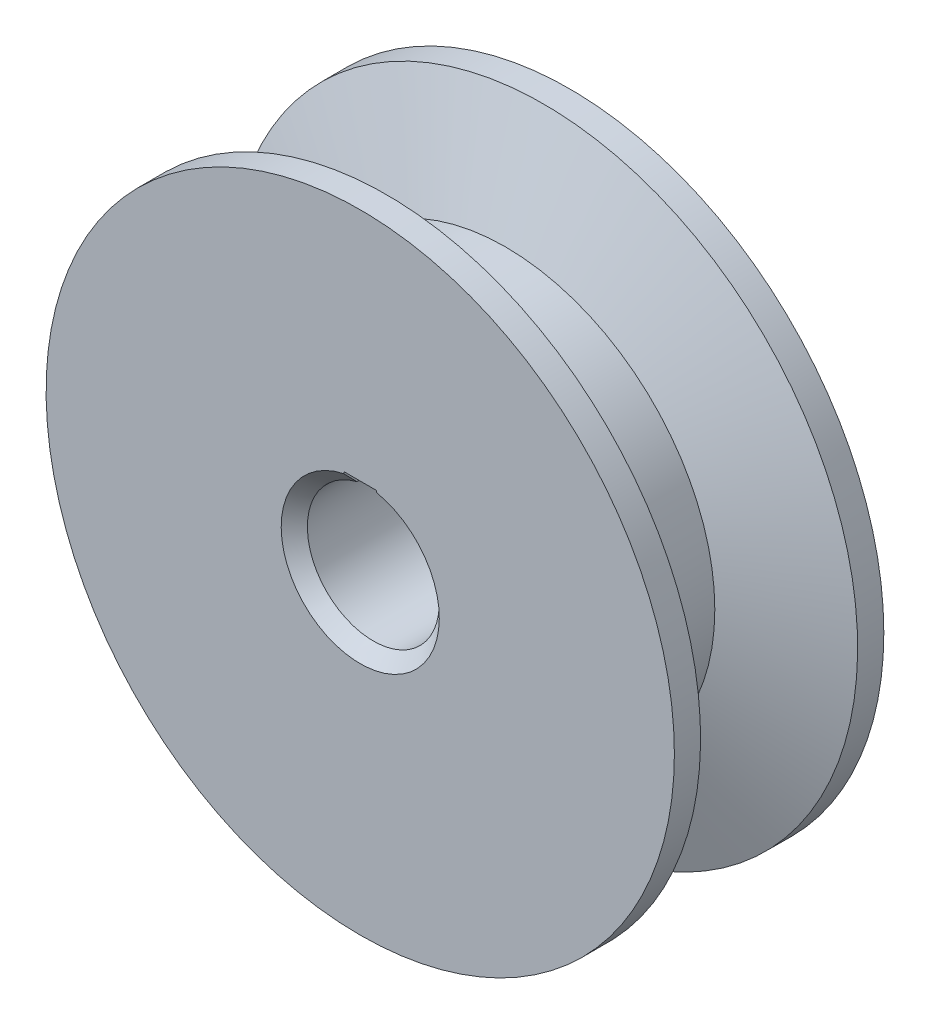
SolidWorks part; units mm, degrees
material "6061-T6 (SS)"
ref_plane "Front Plane" through (0, 0, 0) normal (0, 0, 1) x (1, 0, 0)
ref_plane "Top Plane" through (0, 0, 0) normal (0, 1, 0) x (1, 0, 0)
ref_plane "Right Plane" through (0, 0, 0) normal (1, 0, 0) x (0, 0, -1)
sketch "Sketch1" plane through (0, 0, 0) normal (0, 0, 1) x (1, 0, 0)
  circle A0 centre (0, 0) radius 19.05
  circle A1 centre (0, 0) radius 4
  dimension "D1" = 38.1
  dimension "D2" = 8
extrude "Extrude1" add sketch "Sketch1" along normal mid plane 12.7
sketch "Sketch2" plane through (0, 0, 0) normal (1, 0, 0) x (0, 0, -1)
  line L0 (-4.7625, 19.05) -> (4.7625, 19.05)
  line L2 (4.7625, 19.05) -> (2.4513, 12.7)
  line L3 (2.4513, 12.7) -> (-2.4513, 12.7)
  line L4 (-2.4513, 12.7) -> (-4.7625, 19.05)
  line L5 (-6.35, 0) -> (6.35, 0) construction
  line L6 (-6.35, 19.05) -> (-6.35, -19.05) construction
  line L7 (6.35, -19.05) -> (6.35, 19.05) construction
  point P2 (0, 19.05)
  point P5 (0, 12.7)
  dimension "D1" = 19.05
  dimension "D2" = 6.35
  dimension "D3" = 9.525
  dimension "D4" = 40
chamfer "Chamfer1" distance 0.7937 angle 45 2 edges at (4, 0, -6.35) (4, 0, 6.35)
revolve "Cut-Revolve1" cut sketch "Sketch2" angle 360 about L5
sketch "Sketch3" plane through (0, 0, 6.35) normal (0, 0, 1) x (1, 0, 0)
  line L0 (0, 0) -> (0, 3.8) construction
  line L2 (-1, 4.8) -> (1, 4.8)
  line L3 (-1, 4.8) -> (-1, 2.8)
  line L4 (-1, 2.8) -> (1, 2.8)
  line L5 (1, 4.8) -> (1, 2.8)
  line L6 (-1, 4.8) -> (1, 2.8) construction
  line L7 (-1, 2.8) -> (1, 4.8) construction
  point P10 (0, 0)
  dimension "D1" = 2.8
  dimension "D2" = 2
  dimension "D3" = 2
extrude "Cut-Extrude1" cut sketch "Sketch3" against normal through all contours L4 L5 L2 L3
